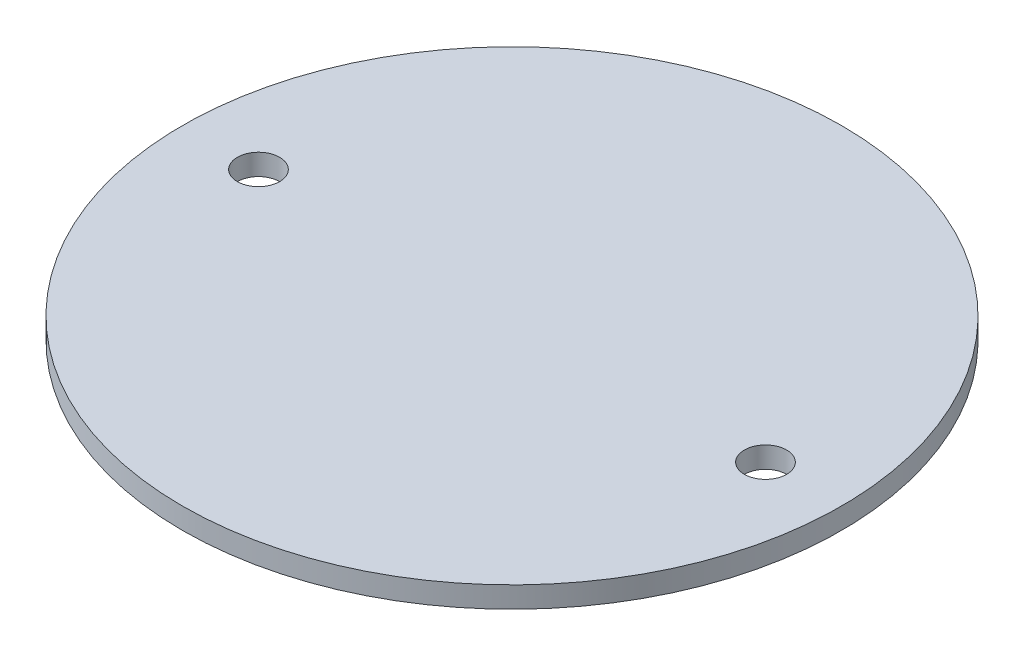
SolidWorks part; units mm, degrees
ref_plane "Front Plane" through (0, 0, 0) normal (0, 0, 1) x (1, 0, 0)
ref_plane "Top Plane" through (0, 0, 0) normal (0, 1, 0) x (1, 0, 0)
ref_plane "Right Plane" through (0, 0, 0) normal (1, 0, 0) x (0, 0, -1)
sketch "Sketch1" plane through (0, 0, 0) normal (0, 1, 0) x (1, 0, 0)
  circle A0 centre (0, 0) radius 49.53
  dimension "D1" = 99.06
extrude "Boss-Extrude1" add sketch "Sketch1" along normal blind 3.175
extrude "Cut-Extrude1" cut sketch "Sketch2" against normal blind 263.398
sketch "Sketch2" plane through (-55.0397, 234.95, -116.0884) normal (0, 1, 0) x (-1, 0, 0)
  circle A0 centre (-93.1397, 116.0884) radius 3.175
  circle A1 centre (-16.9397, 116.0884) radius 3.175
  point P4 (0, 0)
